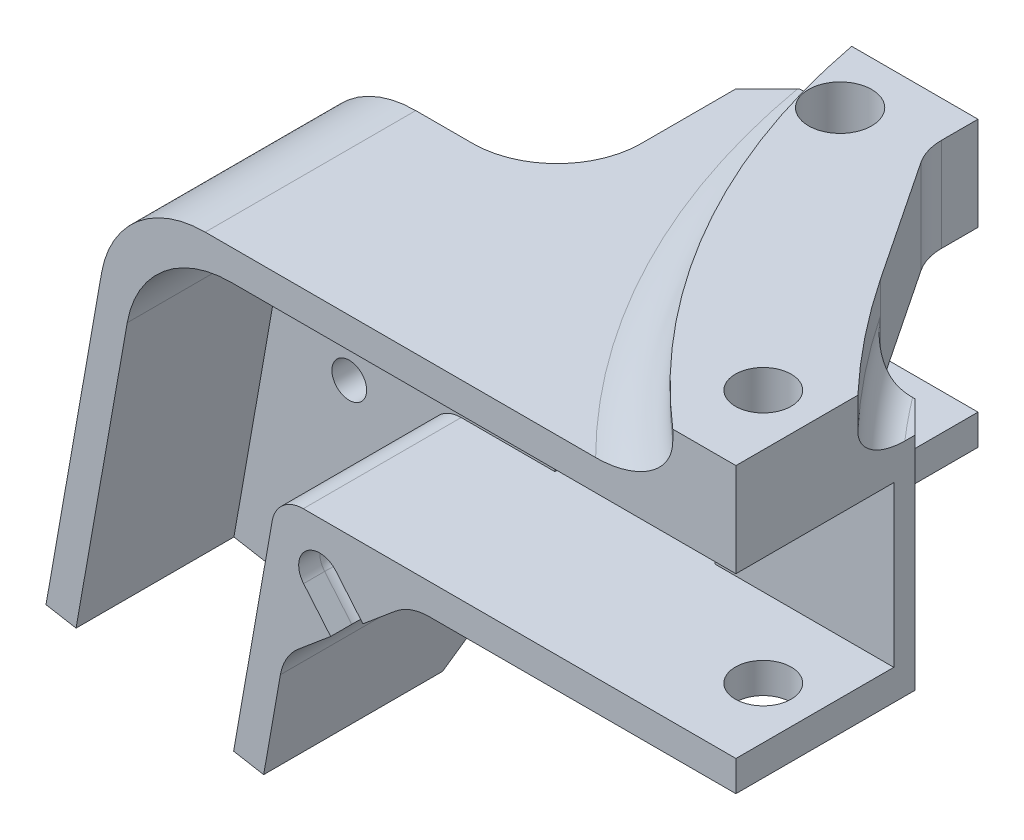
SolidWorks part; units mm, degrees
material "PLA"
ref_plane "前视基准面" through (0, 0, 0) normal (0, 0, 1) x (1, 0, 0)
ref_plane "上视基准面" through (0, 0, 0) normal (0, 1, 0) x (1, 0, 0)
ref_plane "右视基准面" through (0, 0, 0) normal (1, 0, 0) x (0, 0, -1)
sketch "草图1" plane through (0, 0, 0) normal (0, 0, 1) x (1, 0, 0)
  line L0 (0, 0) -> (50, 0) construction
  line L1 (0, 0) -> (-5.2094, -29.5442) construction
  line L2 (50, 10.5) -> (50, -10.5)
  line L3 (50, -10.5) -> (20.8385, -10.5)
  line L4 (17.6245, -11.6698) -> (8.432, -19.3832)
  line L5 (6.7219, -22.3452) -> (5.131, -31.3675)
  line L6 (5.131, -31.3675) -> (-15.5499, -27.7209)
  line L7 (-15.5499, -27.7209) -> (-10.2676, 2.2365)
  line L8 (-0.4195, 10.5) -> (50, 10.5)
  line L9 (13.0283, -15.5265) -> (0, 0) construction
  arc A0 (20.8385, -10.5) -> (17.6245, -11.6698) centre (20.8385, -15.5) ccw
  arc A1 (8.432, -19.3832) -> (6.7219, -22.3452) centre (11.646, -23.2135) ccw
  arc A2 (-10.2676, 2.2365) -> (-0.4195, 10.5) centre (-0.4195, 0.5) cw
  point P17 (50, 0)
  point P20 (-5.2094, -29.5442)
  dimension "D5" = 10
  dimension "D7" = 5
  dimension "D1" = 100
  dimension "D2" = 50
  dimension "D3" = 30
  dimension "D4" = 21
  dimension "D6" = 12
extrude "凸台-拉伸1" add sketch "草图1" against normal blind 20
sketch "草图2" plane through (0, 0, 0) normal (0, 0, 1) x (1, 0, 0)
  line L0 (0, 0) -> (-5.2094, -29.5442) construction
  line L1 (-15.5499, -27.7209) -> (5.131, -31.3675) construction
  line L2 (0, 0) -> (50, 0) construction
  line L3 (50, -10.5) -> (50, 10.5) construction
  line L4 (2.0138, 7.6) -> (50, 7.6)
  line L5 (-7.8342, -0.6635) -> (-12.694, -28.2245)
  line L6 (2.2751, -30.864) -> (5.94, -10.0791)
  line L7 (8.8945, -7.6) -> (50, -7.6)
  line L8 (50, 7.6) -> (50, -7.6)
  line L9 (-12.694, -28.2245) -> (2.2751, -30.864)
  arc A0 (2.0138, 7.6) -> (-7.8342, -0.6635) centre (2.0138, -2.4) ccw
  arc A1 (5.94, -10.0791) -> (8.8945, -7.6) centre (8.8945, -10.6) cw
  dimension "D2" = 10
  dimension "D3" = 3
  dimension "D1" = 15.2
extrude "切除-拉伸1" cut sketch "草图2" against normal blind 15
sketch "草图4" plane through (0, 0, -15) normal (0, 0, 1) x (1, 0, 0)
  line L0 (0, 0) -> (-5.2094, -29.5442) construction
  line L1 (-12.694, -28.2245) -> (2.2751, -30.864) construction
  line L2 (0, 0) -> (50, 0) construction
  line L3 (50, -7.6) -> (50, 7.6) construction
  circle A0 centre (10, 0) radius 1.65
  circle A1 centre (40, 0) radius 1.65
  circle A2 centre (-1.7365, -9.8481) radius 1.65
  circle A3 centre (-4.3412, -24.6202) radius 1.65
  dimension "D1" = 3.3
  dimension "D2" = 15
  dimension "D3" = 10
  dimension "D4" = 10
  dimension "D5" = 30
extrude "切除-拉伸2" cut sketch "草图4" against normal through all
sketch "草图5" plane through (0, 10.5, 0) normal (0, 1, 0) x (1, 0, 0)
  line L1 (50, 20) -> (50, 0) construction
  line L2 (50, 0) -> (-0.4195, 0) construction
  circle A0 centre (45.1, 7.5) radius 2.65
  dimension "D1" = 4.9
  dimension "D2" = 7.5
  dimension "D3" = 5.3
extrude "切除-拉伸3" cut sketch "草图5" against normal through all
sketch "草图9" plane through (0, 0, -20) normal (0, 0, -1) x (-1, 0, 0)
  line L0 (-50, 10.5) -> (0.4195, 10.5) construction
  line L2 (-33, 10.5) -> (-33, -10.5)
  line L3 (-13, 10.5) -> (-13, -10.5)
  line L4 (-18, 10.5) -> (-18, -10.5) construction
  line L5 (-20.8385, -10.5) -> (-50, -10.5) construction
  line L6 (-50, -10.5) -> (-50, 10.5) construction
  line L9 (-33, -10.5) -> (-13, -10.5)
  line L10 (-13, 10.5) -> (-33, 10.5)
  dimension "D1" = 32
  dimension "D2" = 15
  dimension "D4" = 5
extrude "凸台-拉伸3" add sketch "草图9" along normal blind 20
sketch "草图12" plane through (0, 0, -40) normal (0, 0, -1) x (-1, 0, 0)
  line L0 (-33, 10.5) -> (-33, -10.5) construction
  line L1 (-33, 7.6) -> (-17.8, 7.6)
  line L2 (-33, 7.6) -> (-33, -7.6)
  line L3 (-33, -7.6) -> (-17.8, -7.6)
  line L4 (-17.8, 7.6) -> (-17.8, -7.6)
  line L5 (-13, -10.5) -> (-13, 10.5) construction
  point P6 (-17.8, 0)
  point P9 (-13, 0)
  dimension "D1" = 15.2
extrude "切除-拉伸7" cut sketch "草图12" against normal through all
sketch "草图10" plane through (13, 0, 0) normal (-1, 0, 0) x (0, 0, 1)
  line L0 (0, 2.2365) -> (0, -27.7209) construction
  circle A0 centre (-27.4, 0) radius 1.5
  dimension "D1" = 27.4
  dimension "D2" = 3
extrude "切除-拉伸5" cut sketch "草图10" against normal up to next
sketch "草图11" plane through (0, 10.5, 0) normal (0, 1, 0) x (1, 0, 0)
  line L0 (50, 0) -> (-0.4195, 0) construction
  line L1 (33, 40) -> (33, 20) construction
  circle A0 centre (25.5, 34.4) radius 1.65
  dimension "D1" = 34.4
  dimension "D3" = 3.3
  dimension "D2" = 7.5
extrude "切除-拉伸6" cut sketch "草图11" against normal through all
chamfer "倒角1" distance 10 distance2 15 1 edges at (33, 9.05, -20) first distance on face at (41.65, 0, -20)
fillet "圆角2" radius 5 2 edges at (43, 9.05, -20) (33, 9.05, -35)
fillet "圆角3" radius 8 2 edges at (13, 0, -20) (16.9192, -10.5, -20)
chamfer "倒角2" distance 3 angle 45 3 edges at (50, 0, -20) (-5.2094, -29.5442, -20) (13, 0, -40)
sketch "草图13" plane through (0, 0, -20) normal (0, 0, -1) x (-1, 0, 0)
  line L3 (-13, 1.3748) -> (-13, 10.5) construction
  line L5 (-13, 4) -> (-5, 4)
  line L6 (-13, 4) -> (-13, -4)
  line L7 (-13, -4) -> (-5, -4)
  line L8 (-5, 4) -> (-5, -4)
  line L9 (-5, 10.5) -> (-5, -18.5) construction
  point P8 (-5, 0)
  dimension "D1" = 8
extrude "切除-拉伸8" cut sketch "草图13" along normal up to next
sketch "草图14" plane through (0, 0, 0) normal (0, 0, 1) x (1, 0, 0)
  line L0 (11.4962, -16.8121) -> (14.5604, -14.2409)
  line L1 (11.4962, -16.8121) -> (7.6395, -12.2158)
  line L2 (14.5604, -14.2409) -> (10.7036, -9.6447)
  line L3 (7.6395, -12.2158) -> (10.7036, -9.6447)
  line L4 (8.432, -19.3832) -> (17.6245, -11.6698) construction
  line L5 (9.1716, -10.9302) -> (0, 0) construction
  dimension "D1" = 4
  dimension "D2" = 6
extrude "切除-拉伸9" cut sketch "草图14" against normal blind 4
fillet "圆角5" radius 2 1 edges at (9.1716, -10.9302, -4)
fillet "圆角4" radius 2 6 edges at (10.7036, -9.6447, -1) (7.6395, -12.2158, -1) (13.2748, -12.7088, -4) (11.0802, -10.0934, -3.4142) (10.2106, -15.28, -4) (8.016, -12.6646, -3.4142)
sketch "草图15" plane through (0, 10.5, 0) normal (0, 1, 0) x (1, 0, 0)
  line L0 (50, 17) -> (50, 0) construction
  line L11 (33, 40) -> (16, 40)
  line L12 (16, 40) -> (13, 37)
  line L13 (13, 37) -> (13, 28)
  line L14 (5, 20) -> (-0.4195, 20)
  line L15 (-0.4195, 20) -> (-0.4195, 0)
  line L16 (-0.4195, 0) -> (50, 0)
  line L17 (50, 0) -> (50, 17)
  line L18 (50, 17) -> (47, 20)
  line L19 (47, 20) -> (45.6759, 20)
  line L20 (41.5157, 22.2265) -> (33.8397, 33.7404)
  line L21 (33, 36.5139) -> (33, 40)
  line L22 (33, 40) -> (21, 40)
  line L27 (44, 0) -> (50, 0)
  line L28 (50, 0) -> (50, 11.5866)
  line L31 (41.5157, 22.2265) -> (33.8397, 33.7404)
  line L32 (33, 36.5139) -> (33, 40)
  circle A1 centre (45.1, 7.5) radius 2.65 construction
  arc A3 (5, 20) -> (13, 28) centre (5, 28) ccw
  arc A4 (41.5157, 22.2265) -> (45.6759, 20) centre (45.6759, 25) ccw
  arc A5 (33, 36.5139) -> (33.8397, 33.7404) centre (38, 36.5139) ccw
  circle A6 centre (45.1, 7.5) radius 2.65
  arc A8 (33, 36.5139) -> (33.8397, 33.7404) centre (38, 36.5139) ccw
  circle A9 centre (25.5, 34.4) radius 3
  arc A10 (41.5157, 22.2265) -> (50, 11.5866) centre (108.0797, 66.6025) ccw
  arc A12 (21, 40) -> (44, 0) centre (89.7929, 52.9434) ccw
  dimension "D2" = 70
  dimension "D5" = 6
  dimension "D6" = 80
  dimension "D3" = 6
  dimension "D4" = 12
  dimension "D1" = 0
extrude "凸台-拉伸4" add sketch "草图15" along normal blind 6
fillet "圆角6" radius 5 1 edges at (29.1095, 10.5, -18.0505)
fillet "圆角7" radius 3 1 edges at (45.5312, 10.5, -16.7258)
